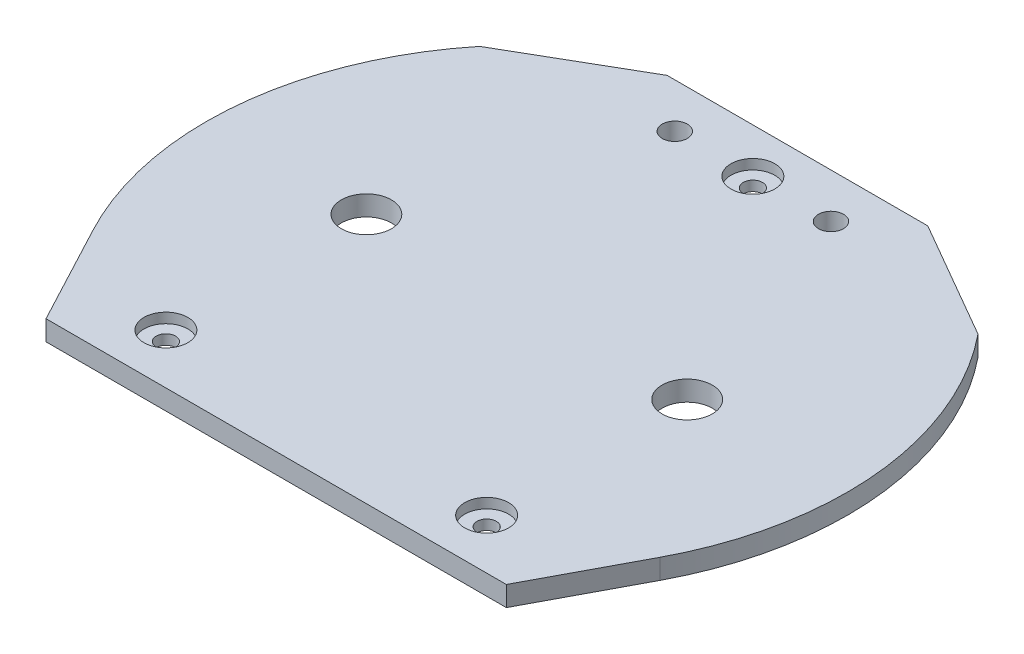
SolidWorks part; units mm, degrees
material "AISI 316 Stainless Steel Sheet (SS)"
ref_plane "Front Plane" through (0, 0, 0) normal (0, 0, 1) x (1, 0, 0)
ref_plane "Top Plane" through (0, 0, 0) normal (0, 1, 0) x (1, 0, 0)
ref_plane "Right Plane" through (0, 0, 0) normal (1, 0, 0) x (0, 0, -1)
sketch "Sketch1" plane through (0, 0, 0) normal (0, 1, 0) x (1, 0, 0)
  line L0 (-40.64, 0) -> (40.64, 0) construction
  line L1 (0, 34.29) -> (0, -31.75) construction
  line L2 (20.32, 0) -> (9.8952, 28.6418) construction
  line L3 (-20.32, 0) -> (-9.8952, 28.6418) construction
  line L5 (-21.813, 34.29) -> (21.813, 34.29)
  line L6 (-35.8986, -19.05) -> (-29.1592, -31.75)
  line L7 (-29.1592, -31.75) -> (29.1592, -31.75)
  line L8 (29.1592, -31.75) -> (35.8986, -19.05)
  line L9 (-31.5651, 25.5979) -> (-16.51, 34.29)
  line L10 (31.5651, 25.5979) -> (16.51, 34.29)
  arc A0 (-21.813, 34.29) -> (-35.8986, -19.05) centre (0, 0) ccw
  circle A3 centre (20.32, 0) radius 3.175
  circle A4 centre (9.8952, 28.6418) radius 1.5875
  circle A5 centre (-20.32, 0) radius 3.175
  circle A6 centre (-9.8952, 28.6418) radius 1.5875
  arc A7 (35.8986, -19.05) -> (21.813, 34.29) centre (0, 0) ccw
  dimension "D1" = 30.48
  dimension "D4" = 6.35
  dimension "D5" = 3.175
  dimension "D6" = 81.28
  dimension "D2" = 70
  dimension "D3" = 20.32
  dimension "D7" = 34.29
  dimension "D8" = 19.05
  dimension "D9" = 12.7
  dimension "D10" = 30
  dimension "D11" = 33.02
extrude "Boss-Extrude1" add sketch "Sketch1" along normal blind 2.54 contours L8 A7 L10 L5 L9 A0 L6 L7 A6 A3 A4 A5 region at (0, 0, -0.2048)
sketch "Sketch4" plane through (0, 2.54, 0) normal (0, 1, 0) x (1, 0, 0)
  point P0 (-9.8952, 28.6418)
  point P1 (0, 28.6418)
  point P2 (20.32, 0)
  point P3 (20.32, -25.4)
  point P6 (-20.32, -25.4)
  point P9 (-20.32, 0)
  dimension "D1" = 6.35
hole_wizard "CBORE for #2 Binding Head Machine Screw1" positions "Sketch5" profile "Sketch6" counterbore size "#2" standard "ANSI Inch" end condition through all
sketch "Sketch5" plane through (0, 2.54, 0) normal (0, 1, 0) x (1, 0, 0)
  point P0 (-20.32, -25.4)
  point P3 (20.32, -25.4)
  point P6 (0, 28.6418)
sketch "Sketch6" plane through (-20.32, 2.54, 25.4) normal (1, 0, 0) x (0, 0, 1)
  line L0 (0, 0) -> (0, 2.54)
  line L1 (0, 2.54) -> (1.2192, 2.54)
  line L3 (1.2192, 2.54) -> (1.2192, 1.27)
  line L4 (1.2192, 1.27) -> (2.7788, 1.27)
  line L5 (2.7788, 1.27) -> (2.7788, 0)
  line L7 (2.7788, 0) -> (0, 0)
  line L11 (0, -6.35) -> (0, 107.95) construction
  dimension "Thru Hole Dia." = 2.4384
  dimension "Thru Hole Depth" = 2.54
  dimension "C'Bore Dia." = 5.5575
  dimension "C'Bore Depth" = 1.27
shell "Shell2" [suppressed] thickness 2.54
sketch "Sketch3" [suppressed] plane through (0, 0, 0) normal (0, -1, 0) x (1, 0, 0)
  line L0 (-36.478, -40.64) -> (-27.7857, 8.89)
  line L1 (-27.7857, 8.89) -> (27.7857, 8.89)
  line L2 (27.7857, 8.89) -> (36.478, -40.64)
  line L3 (36.478, -40.64) -> (-36.478, -40.64)
  circle A0 centre (-20.32, 0) radius 8.89 construction
  circle A1 centre (20.32, 0) radius 8.89 construction
extrude "Cut-Extrude1" [suppressed] cut sketch "Sketch3" against normal up to surface (2.54 mm away)
